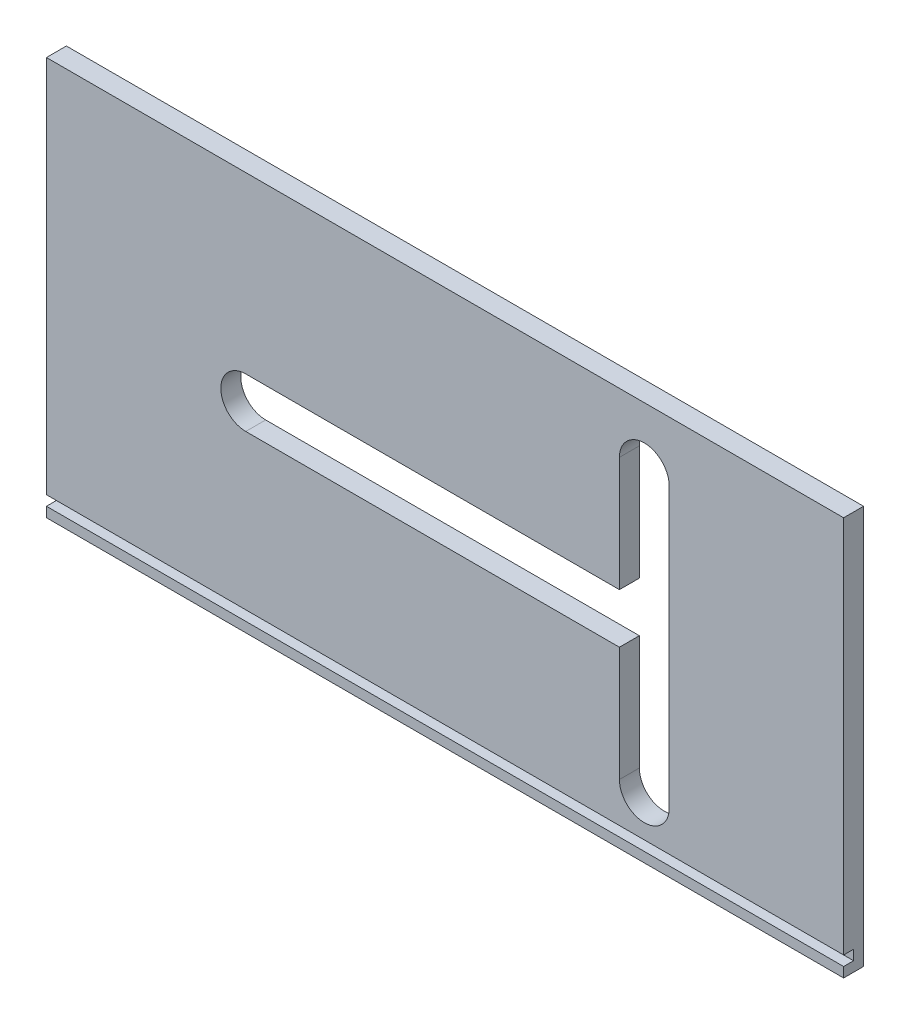
SolidWorks part; units mm, degrees
ref_plane "正面" through (0, 0, 0) normal (0, 0, 1) x (1, 0, 0)
ref_plane "平面" through (0, 0, 0) normal (0, 1, 0) x (1, 0, 0)
ref_plane "右側面" through (0, 0, 0) normal (1, 0, 0) x (0, 0, -1)
sketch "ｽｹｯﾁ1" plane through (0, 0, 0) normal (0, 0, 1) x (1, 0, 0)
  line L1 (-69.2801, 161.5071) -> (330.7199, 161.5071)
  line L2 (-69.2801, 161.5071) -> (-69.2801, -38.4929)
  line L3 (-69.2801, -38.4929) -> (330.7199, -38.4929)
  line L4 (330.7199, 161.5071) -> (330.7199, -38.4929)
  dimension "D1" = 400
  dimension "D3" = 200
extrude "ﾎﾞｽ - 押し出し1" add sketch "ｽｹｯﾁ1" along normal blind 10
sketch "ｽｹｯﾁ2" plane through (0, 0, 10) normal (0, 0, 1) x (1, 0, 0)
  line L0 (330.7199, -38.4929) -> (330.7199, 161.5071) construction
  line L1 (330.7199, -33.4929) -> (-69.2801, -33.4929)
  line L2 (330.7199, -33.4929) -> (330.7199, -28.4929)
  line L3 (330.7199, -28.4929) -> (-69.2801, -28.4929)
  line L4 (-69.2801, -33.4929) -> (-69.2801, -28.4929)
  line L5 (-69.2801, 161.5071) -> (-69.2801, -38.4929) construction
  line L7 (-69.2801, -38.4929) -> (330.7199, -38.4929) construction
  dimension "D1" = 5
  dimension "D2" = 400
  dimension "D3" = 5
extrude "ｶｯﾄ - 押し出し1" cut sketch "ｽｹｯﾁ2" against normal blind 5
sketch "ｽｹｯﾁ3" plane through (0, 0, 10) normal (0, 0, 1) x (1, 0, 0)
  line L0 (30.7199, 57.2394) -> (-69.2801, 57.2394) construction
  line L1 (30.7199, 74.0071) -> (218.2199, 74.0071)
  line L3 (30.7199, 49.0071) -> (218.2199, 49.0071)
  line L4 (218.2199, 131.5071) -> (218.2199, 74.0071)
  line L5 (-69.2801, 161.5071) -> (-69.2801, -28.4929) construction
  line L6 (230.7199, 57.2394) -> (330.7199, 57.2394) construction
  line L7 (330.7199, -28.4929) -> (330.7199, 161.5071) construction
  line L8 (96.6525, 74.0071) -> (96.6525, 161.5071) construction
  line L9 (330.7199, 161.5071) -> (-69.2801, 161.5071) construction
  line L10 (111.609, 49.0071) -> (111.609, -38.4929) construction
  line L11 (-69.2801, -38.4929) -> (330.7199, -38.4929) construction
  line L12 (218.2199, 49.0071) -> (218.2199, -8.4929)
  line L16 (243.2199, 131.5071) -> (243.2199, -8.4929)
  arc A0 (218.2199, 131.5071) -> (243.2199, 131.5071) centre (230.7199, 131.5071) cw
  arc A1 (30.7199, 49.0071) -> (30.7199, 74.0071) centre (30.7199, 61.5071) cw
  arc A2 (218.2199, -8.4929) -> (243.2199, -8.4929) centre (230.7199, -8.4929) ccw
  dimension "D3" = 25
  dimension "D5" = 25
extrude "ｶｯﾄ - 押し出し2" cut sketch "ｽｹｯﾁ3" against normal through all
